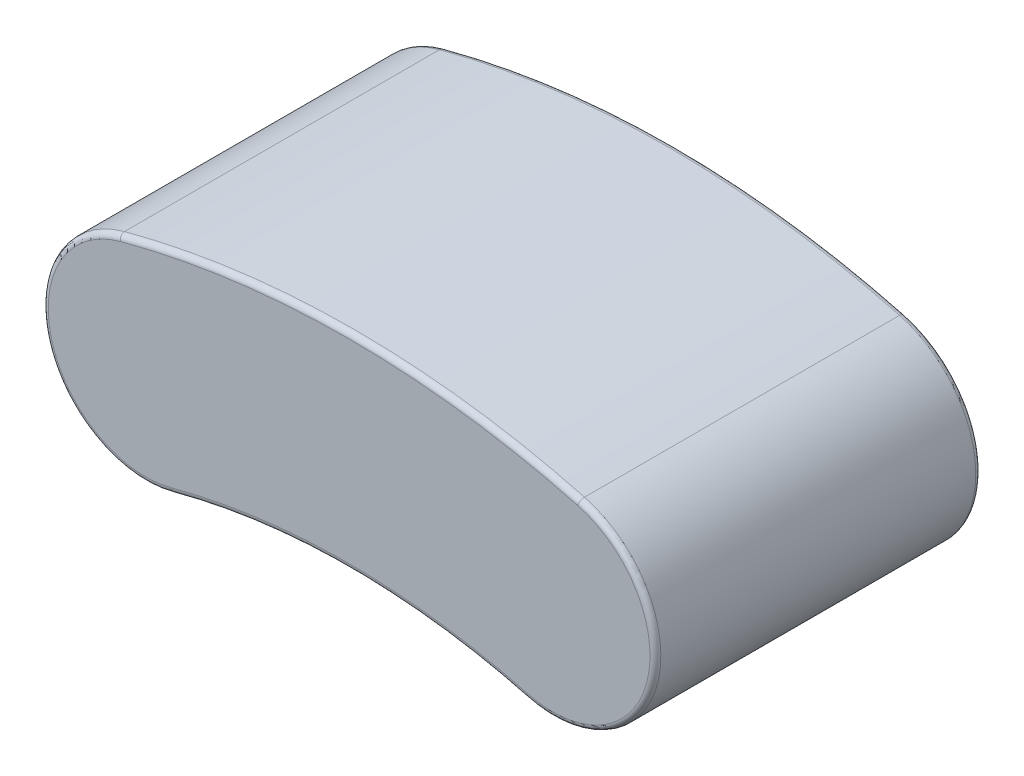
SolidWorks part; units mm, degrees
ref_plane "Plan de face" through (0, 0, 0) normal (0, 0, 1) x (1, 0, 0)
ref_plane "Plan de dessus" through (0, 0, 0) normal (0, 1, 0) x (1, 0, 0)
ref_plane "Plan de droite" through (0, 0, 0) normal (1, 0, 0) x (0, 0, -1)
sketch "Esquisse2" plane through (0, 0, 0) normal (0, 0, 1) x (1, 0, 0)
  arc A0 (-75, -9.8141) -> (75, -9.8141) centre (0, -291.4831) cw construction
  arc A1 (84.7338, 26.742) -> (-84.7338, 26.742) centre (0, -291.4831) ccw
  arc A2 (65.2662, -46.3703) -> (-65.2662, -46.3703) centre (0, -291.4831) ccw
  arc A3 (65.2662, -46.3703) -> (84.7338, 26.742) centre (75, -9.8141) ccw
  arc A4 (-84.7338, 26.742) -> (-65.2662, -46.3703) centre (-75, -9.8141) ccw
  point P3 (0, 0)
  point P8 (0, 0)
  point P11 (93.5328, 0)
  dimension "D2" = 150
  dimension "D3" = 0
extrude "Boss.-Extru.1" add sketch "Esquisse2" along normal blind 120 contours A1 A4 A2 A3
fillet "Congé1" radius 2 4 edges at (111.5561, -19.5479, 120) (0, -37.8298, 120) (-111.5561, -19.5479, 120) (0, 37.8298, 120)
fillet "Congé2" radius 2 4 edges at (111.5561, -19.5479, 0) (0, -37.8298, 0) (-111.5561, -19.5479, 0) (0, 37.8298, 0)
shell "Coque1" thickness 3 removed face at (0, -9.5167, 0)
